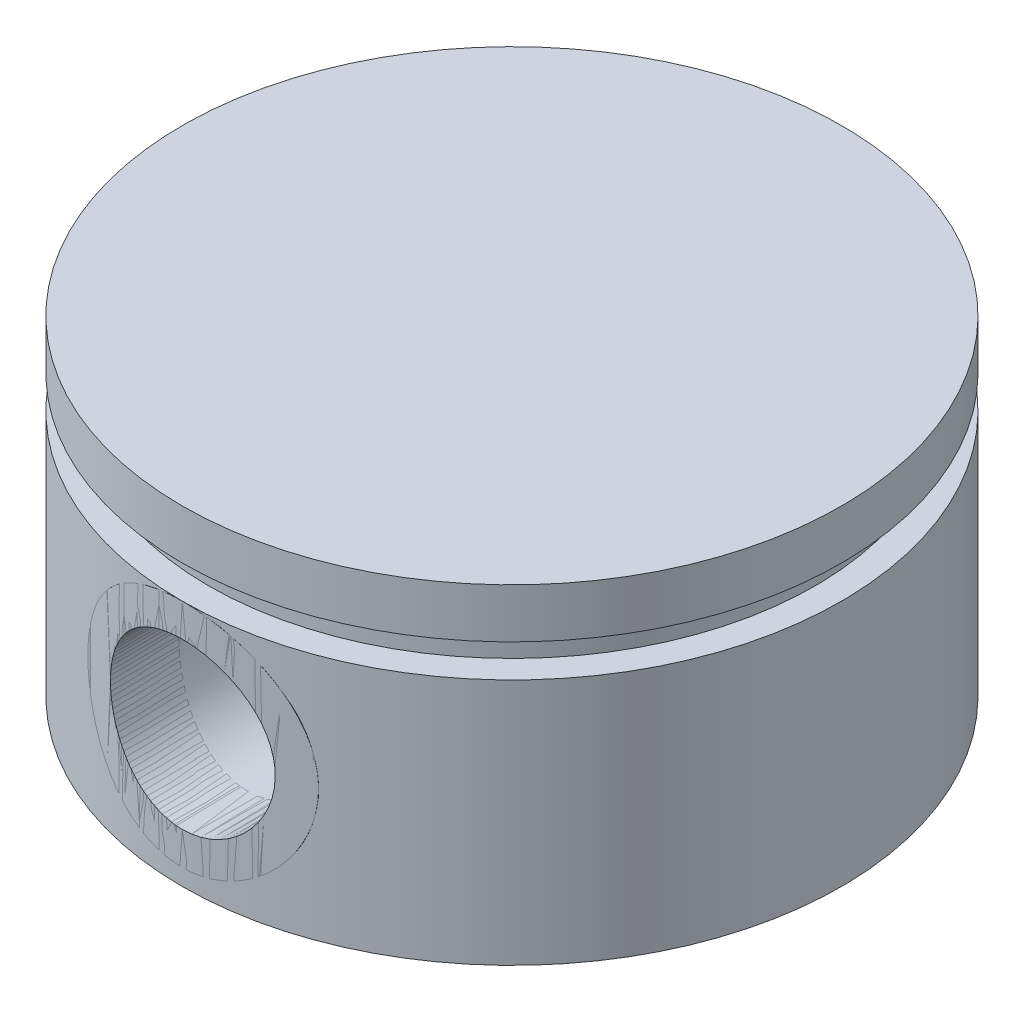
SolidWorks part; units mm, degrees
ref_plane "Plan de face" through (0, 0, 0) normal (0, 0, 1) x (1, 0, 0)
ref_plane "Plan de dessus" through (0, 0, 0) normal (0, 1, 0) x (1, 0, 0)
ref_plane "Plan de droite" through (0, 0, 0) normal (1, 0, 0) x (0, 0, -1)
sketch "Esquisse1" plane through (0, 0, 0) normal (0, 0, 1) x (1, 0, 0)
  line L0 (0, 0) -> (50, 0)
  line L1 (50, 0) -> (50, -50)
  line L2 (0, -10) -> (40, -10)
  line L3 (40, -10) -> (40, -50)
  line L4 (0, 0) -> (0, -10)
  line L5 (50, -7.5) -> (46, -7.5)
  line L6 (50, -7.5) -> (50, -12.5)
  line L7 (50, -12.5) -> (46, -12.5)
  line L8 (46, -7.5) -> (46, -12.5)
  line L9 (40, -50) -> (50, -50)
  dimension "D1" = 50
  dimension "D2" = 50
  dimension "D4" = 5
  dimension "D5" = 4
  dimension "D6" = 7.5
  dimension "D3" = 10
revolve "Révolution1" add sketch "Esquisse1" angle 360 about L4 region at (25, -0.7071, 0)
sketch "Esquisse2" plane through (0, 0, 0) normal (0, 0, 1) x (1, 0, 0)
  line L0 (-50, -50) -> (50, -50) construction
  circle A0 centre (0, -30) radius 12.5
  dimension "D1" = 25
  dimension "D2" = 20
extrude "Enlèv. mat.-Extru.1" cut sketch "Esquisse2" against normal through all both and the other way through all
extrude "Extru.-Mince1" add sketch "Esquisse2<2>" along normal up to surface (21.8375 mm away) from offset 25 separate body thin up to face at (-2.4448, -42.2586, -49.9402) thin type one direction wall 5
sketch "Esquisse2<2>" plane through (0, 0, 0) normal (0, 0, 1) x (1, 0, 0) same geometry as "Esquisse2"
extrude "Extru.-Mince2" add sketch "Esquisse2<3>" against normal up to surface (21.8375 mm away) from offset 25 thin up to face at (-2.4448, -42.2586, -49.9402) offset against normal yes thin type one direction wall 5
sketch "Esquisse2<3>" plane through (0, 0, 0) normal (0, 0, 1) x (1, 0, 0) same geometry as "Esquisse2"
